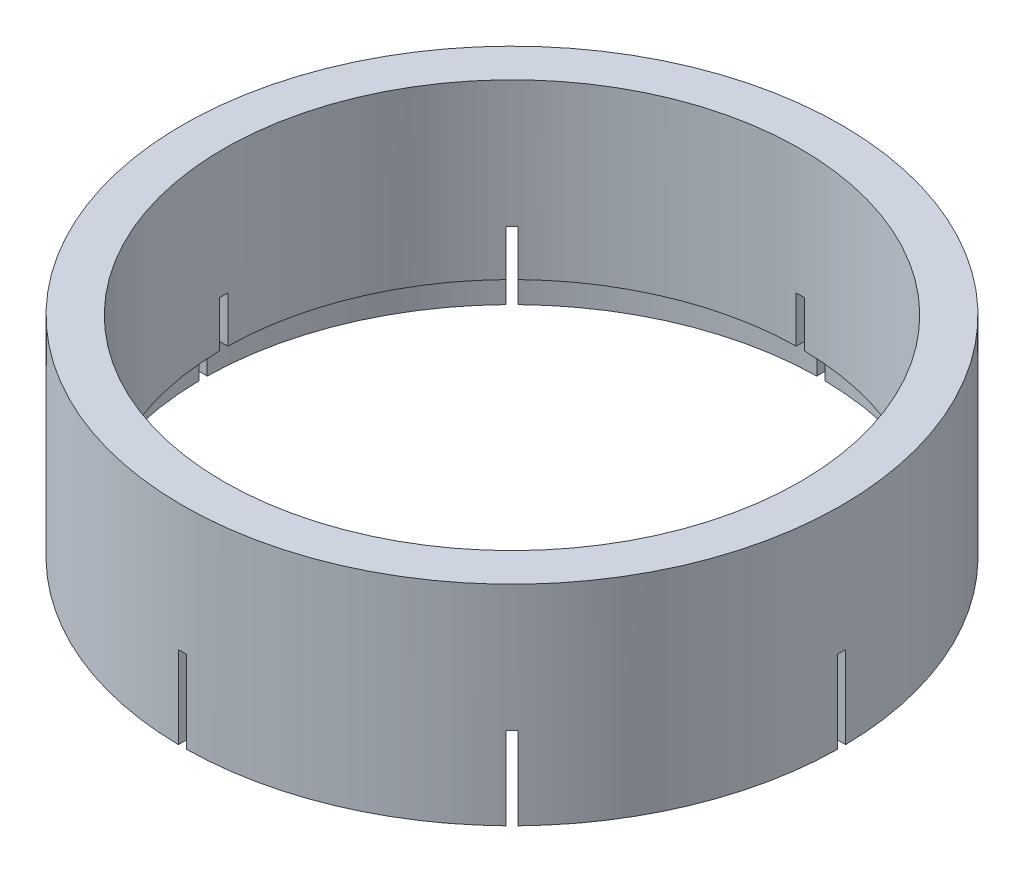
SolidWorks part; units mm, degrees
material "C (Graphite)"
ref_plane "Front Plane" through (0, 0, 0) normal (0, 0, 1) x (1, 0, 0)
ref_plane "Top Plane" through (0, 0, 0) normal (0, 1, 0) x (1, 0, 0)
ref_plane "Right Plane" through (0, 0, 0) normal (1, 0, 0) x (0, 0, -1)
sketch "Sketch1" plane through (0, 0, 0) normal (0, 1, 0) x (1, 0, 0)
  circle A0 centre (0, 0) radius 40
  circle A1 centre (0, 0) radius 35
  dimension "D1" = 80
  dimension "D2" = 70
extrude "Boss-Extrude1" add sketch "Sketch1" along normal blind 25.4
sketch "Sketch2" plane through (0, 0, 0) normal (0, -1, 0) x (1, 0, 0)
  circle A0 centre (0, 0) radius 37.5
  circle A1 centre (0, 0) radius 35
  dimension "D1" = 75
  dimension "D2" = 70
extrude "Cut-Extrude1" cut sketch "Sketch2" against normal blind 4.4
sketch "Sketch3" plane through (0, 0, 0) normal (0, 0, 1) x (1, 0, 0)
  line L0 (44, 0) -> (-44, 0) construction
  line L1 (-0.5, 0) -> (0.5, 0)
  line L2 (-0.5, 0) -> (-0.5, 10)
  line L3 (-0.5, 10) -> (0.5, 10)
  line L4 (0.5, 0) -> (0.5, 10)
  line L5 (0, -13.97) -> (0, 13.97) construction
  point P6 (0, 10)
  dimension "D1" = 0
  dimension "D2" = 1
  dimension "D3" = 10
extrude "Cut-Extrude2" cut sketch "Sketch3" against normal through all both and the other way through all
pattern_circular "CirPattern1" count 4 every 45 about axis through (0, 25.4, 0) along (0, -1, 0) of "Cut-Extrude2"
